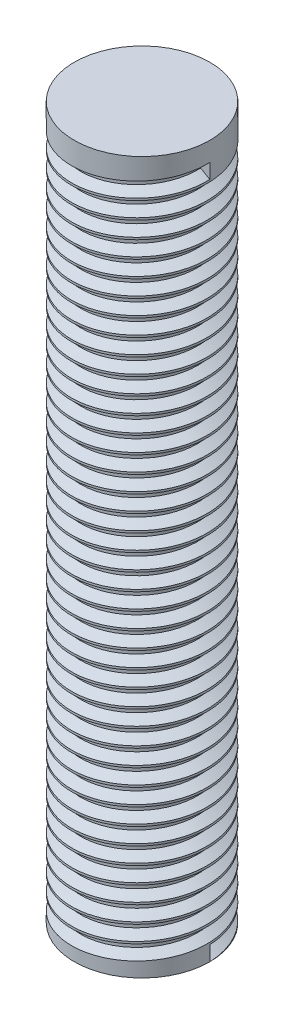
SolidWorks part; units mm, degrees
ref_plane "前视基准面" through (0, 0, 0) normal (0, 0, 1) x (1, 0, 0)
ref_plane "上视基准面" through (0, 0, 0) normal (0, 1, 0) x (1, 0, 0)
ref_plane "右视基准面" through (0, 0, 0) normal (1, 0, 0) x (0, 0, -1)
other "Configuration Table"
sketch "草图1" plane through (0, 0, 0) normal (0, 0, 1) x (1, 0, 0)
  line L0 (0, 0) -> (8, 0)
  line L1 (8, 0) -> (8, 84)
  line L2 (8, 84) -> (0, 84)
  line L3 (0, 84) -> (0, 0)
  line L4 (0, 0) -> (0, 84) construction
  dimension "radius" = 8
  dimension "height" = 84
revolve "Central_screw_blank" add sketch "草图1" angle 360 about L4
thread "Central_right_hand_thread" pitch 2 method cut profile "螺纹线轮廓1" start angle 0, offset 0, length 80, pitch 2, diameter 16
ref_plane "基准面1" through (8, 0, 0) normal (0, 0, 1) x (1, 0, 0)
sketch "螺纹线轮廓1" plane through (8, 0, 0) normal (0, 0, 1) x (1, 0, 0)
  line L0 (0, 0) -> (0, 2) construction
  line L11 (0, 0) -> (0, 1.75)
  line L12 (0, 1.75) -> (-1.0825, 1.125)
  line L13 (-1.0825, 1.125) -> (-1.0825, 0.625)
  line L15 (-1.0825, 0.625) -> (0, 0)
  line L17 (-1.0825, 0.875) -> (0, 0.875) construction
  point P2 (0, 0)
  dimension "Pitch" = 2
  dimension "Profile_Angle" = 60
  dimension "Profile_Land" = 0.5
  dimension "Profile_Height" = 1.0825
